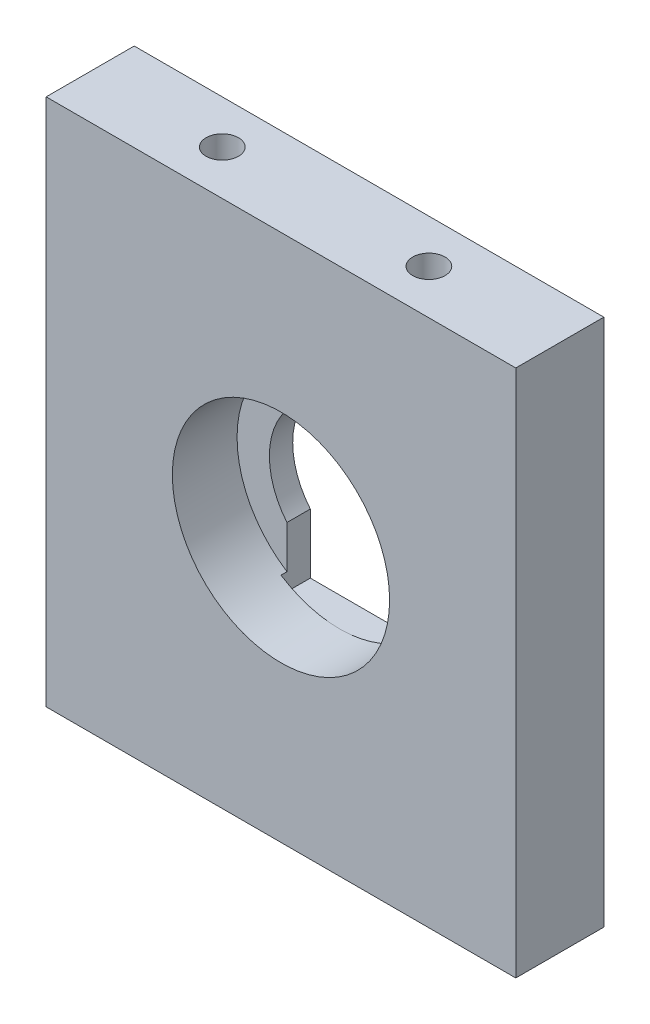
SolidWorks part; units mm, degrees
ref_plane "Front Plane" through (0, 0, 0) normal (1, 0, 0) x (0, 1, 0)
ref_plane "Top Plane" through (0, 0, 0) normal (0, 0, 1) x (0, 1, 0)
ref_plane "Right Plane" through (0, 0, 0) normal (0, 1, 0) x (-1, 0, 0)
sketch "Sketch2" plane through (0, 0, 0) normal (0, 0, 1) x (0, 1, 0)
  line L1 (0, 0) -> (114.3, 0)
  line L2 (0, 0) -> (0, 101.6)
  line L3 (0, 101.6) -> (114.3, 101.6)
  line L4 (114.3, 0) -> (114.3, 101.6)
  dimension "D1" = 114.3
  dimension "D2" = 101.6
extrude "Boss-Extrude2" add sketch "Sketch2" along normal blind 19.05
sketch "Sketch3" plane through (0, 0, 0) normal (0, -1, 0) x (1, 0, 0)
  line L0 (-101.6, 19.05) -> (-101.6, 9.652) construction
  line L1 (-101.6, 19.05) -> (-101.6, 0) construction
  line L2 (-101.6, 9.652) -> (-73.152, 9.652) construction
  line L3 (0, 19.05) -> (0, 9.652) construction
  line L4 (0, 19.05) -> (0, 0) construction
  line L5 (0, 9.652) -> (-28.448, 9.652) construction
  point P6 (-73.152, 9.652)
  point P12 (-28.448, 9.652)
  dimension "D1" = 9.398
  dimension "D2" = 28.448
hole_wizard "M8x1.0 Tapped Hole1" positions "Sketch3" profile "Sketch4" tap size "M8x1.0" standard "ANSI Metric"
sketch "Sketch4" plane through (-28.448, 0, 9.652) normal (1, 0, 0) x (0, 0, -1)
  line L0 (0, 0) -> (0, 21.153)
  line L1 (0, 21.153) -> (3.5, 19.05)
  line L2 (3.5, 19.05) -> (3.5, 0)
  line L5 (3.5, 0) -> (0, 0)
  line L10 (0, 21.153) -> (-3.5, 19.05) construction
  line L11 (0, -6.35) -> (0, 107.95) construction
  dimension "Tap Drill Dia." = 7
  dimension "Tap Drill Depth" = 19.05
  dimension "Drill Angle" = 118
cosmetic thread "Hole Thread1" parameters "D1"=16.002, "D2"=8
cosmetic thread "Hole Thread2" parameters "D1"=16.002, "D2"=8
sketch "Sketch5" plane through (0, 114.3, 0) normal (0, 1, 0) x (-1, 0, 0)
  line L0 (0, 0) -> (28.448, 0) construction
  line L1 (0, 0) -> (101.6, 0) construction
  line L2 (28.448, 0) -> (28.448, 9.398) construction
  line L3 (101.6, 0) -> (73.152, 0) construction
  line L4 (73.152, 0) -> (73.152, 9.398) construction
  point P10 (28.448, 9.398)
  point P11 (73.152, 9.398)
  dimension "D1" = 28.448
  dimension "D2" = 9.398
hole_wizard "M8x1.0 Tapped Hole2" positions "Sketch5" profile "Sketch6" tap size "M8x1.0" standard "ANSI Metric"
sketch "Sketch6" plane through (-73.152, 114.3, 9.398) normal (1, 0, 0) x (0, 0, 1)
  line L0 (0, 0) -> (0, 21.153)
  line L1 (0, 21.153) -> (3.5, 19.05)
  line L2 (3.5, 19.05) -> (3.5, 0)
  line L5 (3.5, 0) -> (0, 0)
  line L10 (0, 21.153) -> (-3.5, 19.05) construction
  line L11 (0, -6.35) -> (0, 107.95) construction
  dimension "Tap Drill Dia." = 7
  dimension "Tap Drill Depth" = 19.05
  dimension "Drill Angle" = 118
cosmetic thread "Hole Thread3" parameters "D1"=16.002, "D2"=8
cosmetic thread "Hole Thread4" parameters "D1"=16.002, "D2"=8
sketch "Sketch7" plane through (0, 0, 19.05) normal (0, 0, 1) x (1, 0, 0)
  line L0 (-101.6, 57.15) -> (0, 57.15) construction
  line L1 (-101.6, 114.3) -> (-101.6, 0) construction
  line L2 (0, 0) -> (0, 114.3) construction
  circle A0 centre (-50.8, 57.15) radius 23.5
  dimension "D1" = 47
extrude "Cut-Extrude1" cut sketch "Sketch7" against normal blind 14
sketch "Sketch8" plane through (0, 0, 0) normal (0, 0, -1) x (1, 0, 0)
  line L0 (-50.8, -114.3) -> (-50.8, -80.65) construction
  line L1 (0, -114.3) -> (-101.6, -114.3) construction
  line L2 (-50.8, 0) -> (-50.8, -33.65) construction
  line L3 (-101.6, 0) -> (0, 0) construction
  line L4 (-63.5, -33.65) -> (-38.1, -33.65)
  line L8 (-63.5, -80.65) -> (-38.1, -80.65)
  line L9 (-38.1, -80.65) -> (-38.1, -33.65)
  line L11 (-63.5, -33.65) -> (-63.5, -80.65)
  circle A0 centre (-50.8, -57.15) radius 23.5 construction
  point P14 (-50.8, -33.65)
  point P15 (-35.56, -34.4793)
  point P16 (-66.04, -34.4793)
  point P19 (-50.8, -80.65)
  point P20 (0, 0)
  dimension "D1" = 25.4
extrude "Cut-Extrude3" cut sketch "Sketch8" against normal blind 6.35
sketch "Sketch10" plane through (0, 0, 0) normal (0, 0, -1) x (1, 0, 0)
  line L0 (-101.6, 0) -> (-101.6, -57.15) construction
  line L1 (-101.6, -114.3) -> (-101.6, 0) construction
  line L2 (-101.6, -57.15) -> (-50.8, -57.15) construction
  circle A0 centre (-50.8, -57.15) radius 16.51
  dimension "D1" = 33.02
extrude "Cut-Extrude4" cut sketch "Sketch10" against normal through all
